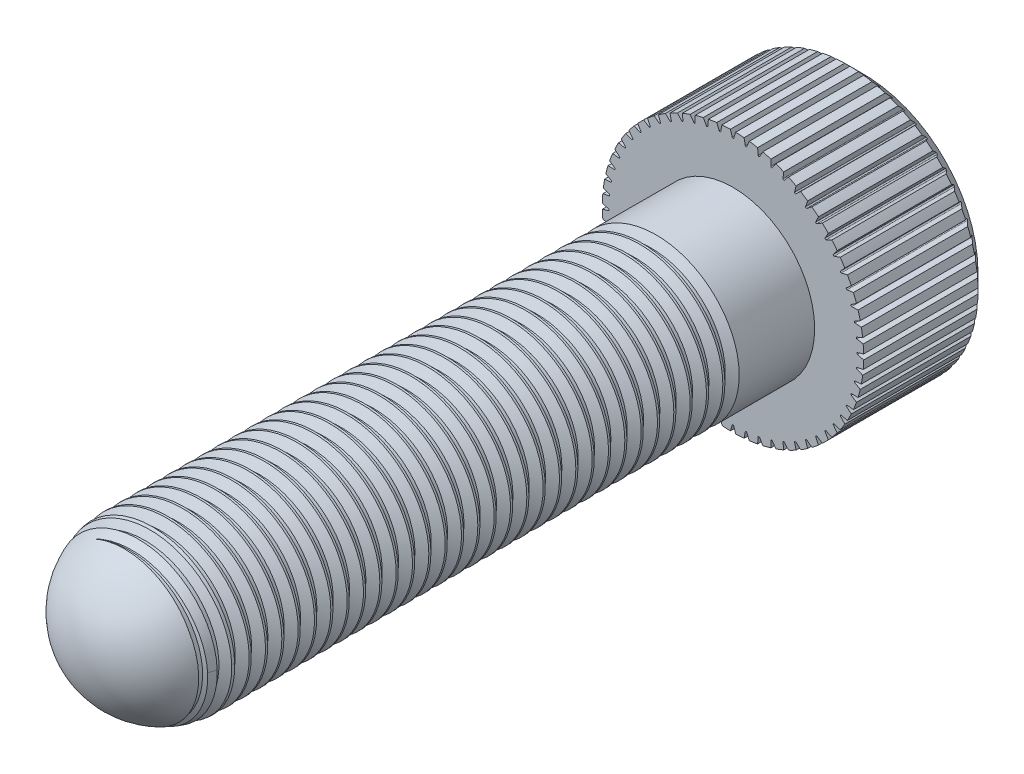
SolidWorks part; units mm, degrees
material "AISI 304"
ref_plane "Front Plane" through (0, 0, 0) normal (0, 0, 1) x (1, 0, 0)
ref_plane "Top Plane" through (0, 0, 0) normal (0, 1, 0) x (1, 0, 0)
ref_plane "Right Plane" through (0, 0, 0) normal (1, 0, 0) x (0, 0, -1)
sketch "Sketch1" plane through (0, 0, 0) normal (0, 0, 1) x (1, 0, 0)
  circle A0 centre (0, 0) radius 4
  circle A1 centre (0, 0) radius 2.5
  dimension "D1" = 8
  dimension "D2" = 5
extrude "Boss-Extrude1" add sketch "Sketch1" along normal blind 20 contours A1
extrude "Boss-Extrude2" add sketch "Sketch1<3>" against normal blind 4 contours A0
sketch "Sketch1<3>" plane through (0, 0, 0) normal (0, 0, 1) x (1, 0, 0) same geometry as "Sketch1"
fillet "Fillet4" radius 2.5 1 edges at (2.5, 0, 20)
thread "Thread5" pitch 0.5 method cut profile "Thread Profile5" start angle 0, offset 2, length 17, pitch 0.5, diameter 5
ref_plane "Plane5" through (-2.5, 0, 19.5) normal (0, -1, 0) x (-1, 0, 0)
sketch "Thread Profile5" plane through (-2.5, 0, 19.5) normal (0, -1, 0) x (-1, 0, 0)
  line L0 (0, 0) -> (0, 0.5) construction
  line L11 (0, 0) -> (0, 0.4368)
  line L12 (0, 0.4368) -> (-0.27, 0.2809)
  line L13 (-0.27, 0.2809) -> (-0.27, 0.1559)
  line L15 (-0.27, 0.1559) -> (0, 0)
  line L17 (-0.27, 0.2184) -> (0, 0.2184) construction
  point P2 (0, 0)
  dimension "Pitch" = 0.5
  dimension "Profile_Angle" = 60
  dimension "Profile_Land" = 0.125
  dimension "Profile_Height" = 0.27
chamfer "Chamfer1" distance 0.5 angle 45 1 edges at (4, 0, -4)
sketch "Sketch2" plane through (0, 0, -4) normal (0, 0, -1) x (-1, 0, 0)
  line L0 (0, 4) -> (0, 0) construction
  line L1 (-0.08, 3.9992) -> (-0.0239, 3.8142)
  line L2 (0.08, 3.9992) -> (0.0239, 3.8142)
  circle A0 centre (0, 0) radius 4 construction
  arc A1 (0.08, 3.9992) -> (-0.08, 3.9992) centre (0, 0) ccw
  arc A2 (-0.0239, 3.8142) -> (0.0239, 3.8142) centre (0, 3.8215) ccw
  dimension "D1" = 0.05
  dimension "D2" = 0.08
extrude "Cut-Extrude1" cut sketch "Sketch2" against normal up to surface (4 mm away) up to face at (2.5, 0, 0)
pattern_circular "CirPattern1" count 60 over 360 about axis through (0, 0, -4) along (0, 0, -1) of "Cut-Extrude1"
sketch "Sketch3" plane through (0, 0, 0) normal (0, 1, 0) x (1, 0, 0)
  line L0 (0, 9.2764) -> (0, -26.5982) construction
